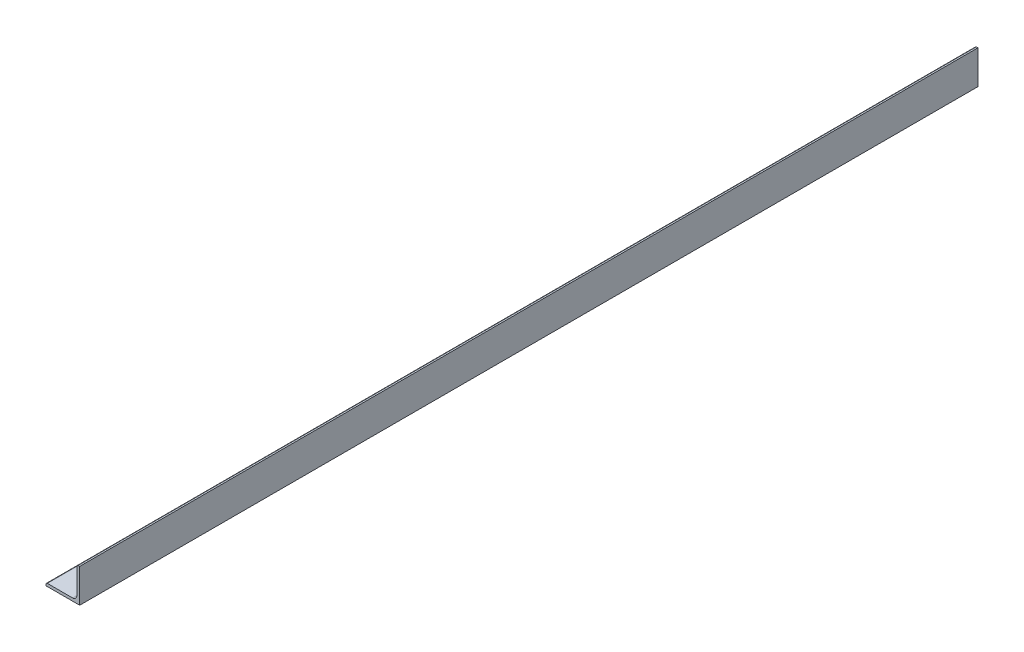
SolidWorks part; units mm, degrees
ref_plane "Front Plane" through (0, 0, 0) normal (0, 0, 1) x (1, 0, 0)
ref_plane "Top Plane" through (0, 0, 0) normal (0, 1, 0) x (1, 0, 0)
ref_plane "Right Plane" through (0, 0, 0) normal (1, 0, 0) x (0, 0, -1)
sketch "Sketch0" plane through (0, 0, 0) normal (0, 0, 1) x (1, 0, 0)
  line L0 (-9.525, -9.525) -> (9.525, -9.525)
  line L1 (9.525, -9.525) -> (9.525, 9.525)
  line L2 (9.525, 0) -> (0, 0) construction
  line L3 (0, 0) -> (0, -9.525) construction
  line L4 (7.9375, -5.5499) -> (7.9375, 9.525) construction
  line L5 (5.5499, -7.9375) -> (-9.525, -7.9375) construction
  arc A0 (7.9375, -5.5499) -> (5.5499, -7.9375) centre (5.5499, -5.5499) cw
  point P3 (7.2382, -7.2382)
  dimension "Inside Corner Radius" = 2.3876
  dimension "Outside Height" = 19.05
  dimension "Inside Height" = 17.4625
  dimension "Inside Width" = 17.4625
  dimension "Wall Thickness" = 1.5875
  dimension "D1" = 1.5875
  dimension "Outside Width" = 19.05
sketch "Sketch1" plane through (0, 0, 0) normal (1, 0, 0) x (0, 0, -1)
  line L0 (254, 0) -> (-254, 0)
  point P4 (0, 0)
  dimension "Length" = 508
sketch "Sketch2" plane through (0, 0, 0) normal (0, 0, 1) x (1, 0, 0)
  line L0 (-9.525, -9.525) -> (9.525, -9.525)
  line L1 (9.525, -9.525) -> (9.525, 9.525)
  line L2 (9.525, 9.525) -> (7.9375, 9.525) construction
  line L3 (7.9375, 8.7313) -> (7.9375, -5.5499)
  line L4 (5.5499, -7.9375) -> (-8.7313, -7.9375)
  line L5 (-9.525, -9.525) -> (-9.525, -7.9375) construction
  line L6 (8.7313, 9.525) -> (9.525, 9.525)
  line L7 (-9.525, -8.7313) -> (-9.525, -9.525)
  line L8 (9.525, 0) -> (0, 0) construction
  line L9 (0, 0) -> (0, -9.525) construction
  arc A0 (7.9375, 8.7313) -> (8.7313, 9.525) centre (8.7313, 8.7313) cw
  arc A1 (-9.525, -8.7313) -> (-8.7313, -7.9375) centre (-8.7313, -8.7313) cw
  arc A2 (7.9375, -5.5499) -> (5.5499, -7.9375) centre (5.5499, -5.5499) cw
  dimension "Inside Radius" = 2.3876
  dimension "Height" = 19.05
  dimension "Width" = 19.05
  dimension "Thickness" = 1.5875
extrude "Boss-Extrude1" add sketch "Sketch2" along normal mid plane 508
sketch "Break Locations" plane through (0, 0, 0) normal (1, 0, 0) x (0, 0, -1)
  line L0 (-234.569, 0) -> (234.569, 0)
  line L1 (-254, -9.525) -> (-254, 9.525) construction
  line L2 (254, -9.525) -> (254, 9.525) construction
  point P0 (-237.8075, 0)
  point P1 (237.8075, 0)
  point P10 (0, 0)
  point P11 (234.569, 0)
  point P13 (-234.569, 0)
  dimension "D1" = 16.1925
  dimension "D2" = 16.1925
  dimension "D3" = 19.431
hole_wizard "#10 Clearance Hole1" positions "Sketch3" profile "Sketch4" hole size "#10" standard "ANSI Inch"
sketch "Sketch3" plane through (0, -9.525, 0) normal (0, -1, 0) x (-1, 0, 0)
  point P2 (-3.1368, 241.5017)
  point P5 (-3.1368, 216.1017)
  point P8 (-2.9733, -241.2618)
  point P11 (-2.9733, -215.9)
sketch "Sketch4" plane through (3.1368, -9.525, -241.5017) normal (1, 0, 0) x (0, 0, -1)
  line L0 (0, 0) -> (0, 4.7977)
  line L1 (0, 4.7977) -> (2.4892, 3.302)
  line L2 (2.4892, 3.302) -> (2.4892, 0)
  line L5 (2.4892, 0) -> (0, 0)
  line L10 (0, 4.7977) -> (-2.4892, 3.302) construction
  line L11 (0, -6.35) -> (0, 107.95) construction
  dimension "Hole Dia." = 4.9784
  dimension "Hole Depth" = 3.302
  dimension "Drill Angle" = 118
equation "\"D1@Break Locations\" = .85 * \"Height@Sketch2\""
equation "\"D2@Break Locations\"=\"D1@Break Locations\""
equation "\"Thickness@Sketch2\"=\"wall thickness@sketch0\""
equation "\"Height@Sketch2\"=\"outside height@sketch0\""
equation "\"Width@Sketch2\"=\"outside width@sketch0\""
equation "\"Inside Radius@Sketch2\"=\"inside corner radius@sketch0\""
equation "\"Length@Boss-Extrude1\"=\"length@sketch1\""
equation "\"D3@Break Locations\"=\"D2@Break Locations\"*1.2"
equation "\"D1@Sketch0\"=\"Wall Thickness@Sketch0\""
